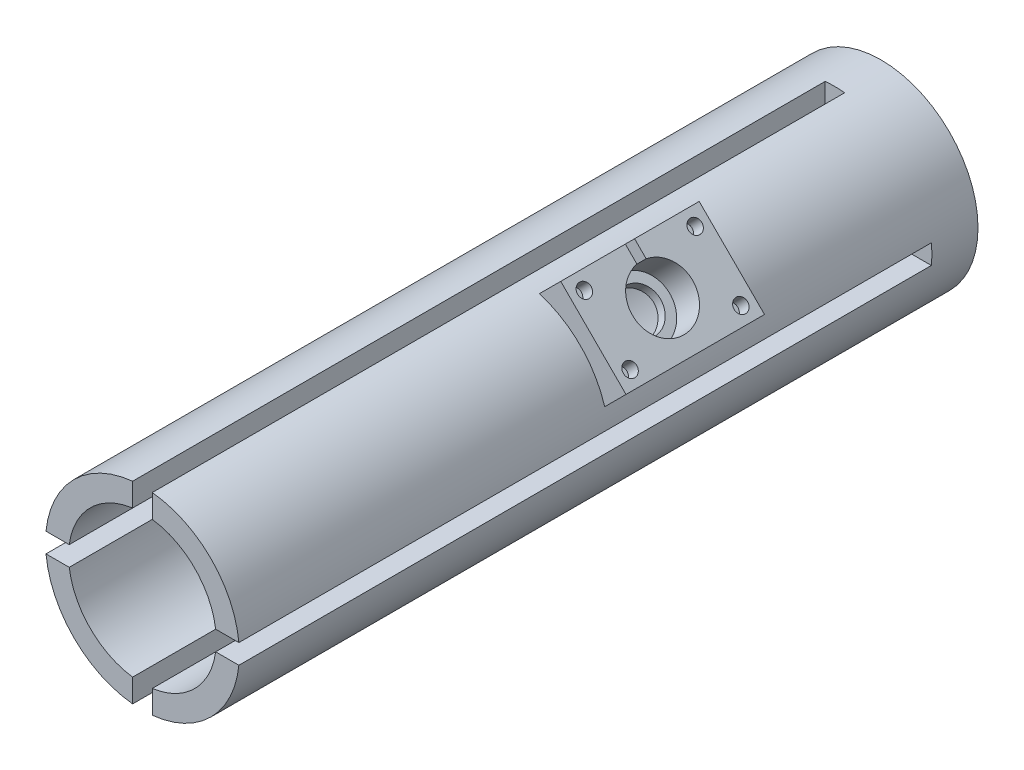
SolidWorks part; units mm, degrees
ref_plane "Front Plane" through (0, 0, 0) normal (0, 0, 1) x (1, 0, 0)
ref_plane "Top Plane" through (0, 0, 0) normal (0, 1, 0) x (1, 0, 0)
ref_plane "Right Plane" through (0, 0, 0) normal (1, 0, 0) x (0, 0, -1)
sketch "Sketch1" plane through (0, 0, 0) normal (0, 0, 1) x (1, 0, 0)
  line L0 (-26.67, 0) -> (26.67, 0) construction
  line L1 (0, 26.67) -> (0, -26.67) construction
  line L7 (-15.24, 2.6988) -> (-27.94, 2.6987)
  line L8 (-15.24, 2.6988) -> (-15.24, -2.6987)
  line L11 (-15.24, -2.6987) -> (-27.94, -2.6987)
  line L12 (-27.94, 2.6987) -> (-27.94, -2.6987)
  line L17 (-15.24, 2.6988) -> (-27.94, -2.6987) construction
  line L18 (-15.24, -2.6987) -> (-27.94, 2.6987) construction
  line L23 (2.6987, 15.24) -> (-2.6988, 15.24)
  line L24 (-2.6988, 15.24) -> (-2.6988, 27.94)
  line L26 (2.6987, 15.24) -> (2.6987, 27.94)
  line L27 (2.6987, 27.94) -> (-2.6988, 27.94)
  line L28 (2.6987, 15.24) -> (-2.6988, 27.94) construction
  line L29 (-2.6988, 15.24) -> (2.6987, 27.94) construction
  line L30 (26.67, 0) -> (-26.67, 0) construction
  line L31 (15.24, -2.6987) -> (15.24, 2.6988)
  line L32 (15.24, 2.6988) -> (27.94, 2.6988)
  line L33 (15.24, -2.6987) -> (27.94, -2.6987)
  line L34 (27.94, -2.6987) -> (27.94, 2.6988)
  line L35 (15.24, -2.6987) -> (27.94, 2.6988) construction
  line L36 (15.24, 2.6988) -> (27.94, -2.6987) construction
  line L37 (0, -26.67) -> (0, 26.67) construction
  line L38 (-2.6987, -15.24) -> (2.6988, -15.24)
  line L39 (2.6988, -15.24) -> (2.6988, -27.94)
  line L40 (-2.6987, -15.24) -> (-2.6987, -27.94)
  line L41 (-2.6987, -27.94) -> (2.6988, -27.94)
  line L42 (-2.6987, -15.24) -> (2.6988, -27.94) construction
  line L43 (2.6988, -15.24) -> (-2.6987, -27.94) construction
  line L44 (-18.8585, -18.8585) -> (18.5639, 18.5639) construction
  line L45 (7.1842, 25.1447) -> (25.1447, 7.1842)
  line L46 (7.1842, 25.1447) -> (13.4704, 31.4309)
  line L47 (25.1447, 7.1842) -> (31.4309, 13.4704)
  line L48 (13.4704, 31.4309) -> (31.4309, 13.4704)
  line L49 (22.4506, 22.4506) -> (16.1645, 16.1645) construction
  circle A10 centre (0, 0) radius 20.32
  circle A14 centre (0, 0) radius 26.67
  circle A15 centre (0, 0) radius 10.16
  point P7 (-21.59, 0)
  point P33 (0, 0)
  dimension "D1" = 40.64
  dimension "D4" = 12.7
  dimension "D5" = 4
  dimension "D7" = 45
  dimension "D8" = 25.4
  dimension "D9" = 8.89
  dimension "D6" = 20.32
  dimension "D10" = 22.86
  dimension "D11" = 15.24
  dimension "D3" = 5.3975
  dimension "D2" = 6.35
extrude "Boss-Extrude2" add sketch "Sketch1" along normal blind 203.2 contours L24 A14 L7 A10 | L47 A14 L46 L45 A10 | L32 A14 L47 L45 L46 L26 A10 | L39 A14 L33 A10 | L11 A14 L40 A10 region at (-15.5039, 15.5039, 0) region at (-15.5039, -15.5039, 0) region at (14.5551, 14.5551, 0) region at (15.5039, -15.5039, 0) region at (17.2574, 17.2574, 0)
extrude "Boss-Extrude3" add sketch "Sketch1<15>" along normal blind 12.7 contours L7 A10 L11 L8 | L26 A10 L24 L23 | L33 A10 L32 L31 | L40 A10 L39 L38 | L39 A14 L33 A10 | L11 A14 L40 A10 | L24 A14 L7 A10 | L32 A14 L47 L45 L46 L26 A10 | L47 A14 L46 L45 | L32 A10 L26 L23 L24 L7 L8 L11 L40 L38 L39 L33 L31 A15 | L26 A14 L24 A10 | L7 A14 L11 A10 | L40 A14 L39 A10 | L33 A14 L32 A10 region at (-17.7503, 0, 0) region at (-17.69, 3.2684, 0) region at (-23.4422, 0, 0) region at (-15.5039, 15.5039, 0) region at (0, 17.7503, 0) region at (0, 23.4422, 0) region at (-15.5039, -15.5039, 0) region at (14.5551, 14.5551, 0) region at (0, -23.4422, 0) region at (0, -17.7503, 0) region at (17.7503, 0, 0) region at (23.4422, 0, 0) region at (15.5039, -15.5039, 0) region at (17.2574, 17.2574, 0)
sketch "Sketch1<15>" plane through (0, 0, 0) normal (0, 0, 1) x (1, 0, 0) same geometry as "Sketch1"
extrude "Boss-Extrude4" add sketch "Sketch1<18>" along normal blind 101.6 contours A14 L47 L48 L46 region at (20.2329, 20.2329, 0)
sketch "Sketch1<18>" plane through (0, 0, 0) normal (0, 0, 1) x (1, 0, 0) same geometry as "Sketch1"
extrude "Cut-Extrude2" cut sketch "Sketch1<19>" along normal blind 63.5 contours A14 L47 L48 L46 region at (20.2329, 20.2329, 0)
sketch "Sketch1<19>" plane through (0, 0, 0) normal (0, 0, 1) x (1, 0, 0) same geometry as "Sketch1"
sketch "Sketch4" plane through (22.4506, 22.4506, 0) normal (0.7071, 0.7071, 0) x (0, 0, -1)
  line L0 (-82.55, -12.7) -> (-82.55, 12.7) construction
  line L1 (-101.6, -12.7) -> (-63.5, -12.7) construction
  line L2 (-101.6, 12.7) -> (-63.5, 12.7) construction
  circle A0 centre (-82.55, 0) radius 8.3
  dimension "D1" = 16.6
extrude "Cut-Extrude3" cut sketch "Sketch4" against normal blind 8.89
sketch "Sketch5" plane through (22.4506, 22.4506, 0) normal (0.7071, 0.7071, 0) x (0, 0, -1)
  line L0 (-82.55, -12.7) -> (-82.55, 12.7) construction
  line L4 (-63.5, -12.7) -> (-63.5, 12.7)
  line L5 (-63.5, 12.7) -> (-101.6, 12.7)
  line L6 (-101.6, 12.7) -> (-101.6, -12.7)
  line L7 (-101.6, -12.7) -> (-63.5, -12.7)
  line L9 (-63.5, 12.7) -> (-101.6, 12.7)
  line L10 (-101.6, 12.7) -> (-101.6, -12.7)
  line L11 (-101.6, -12.7) -> (-63.5, -12.7)
  line L14 (-63.5, -12.7) -> (-63.5, 12.7)
  circle A1 centre (-95.25, -5.715) radius 1.5875 construction
  circle A2 centre (-95.25, 5.715) radius 1.5875 construction
  circle A4 centre (-95.25, -5.715) radius 1.5875 construction
  circle A5 centre (-95.25, 5.715) radius 1.5875 construction
  circle A6 centre (-69.85, 5.715) radius 1.5875 construction
  circle A7 centre (-69.85, -5.715) radius 1.5875 construction
  circle A8 centre (-95.25, -5.715) radius 2.5781
  circle A9 centre (-95.25, 5.715) radius 2.5781
  circle A10 centre (-69.85, 5.715) radius 2.5781
  circle A11 centre (-69.85, -5.715) radius 2.5781
  circle A12 centre (-82.55, 0) radius 5.715
  dimension "D2" = 5.1562
  dimension "D3" = 11.43
  dimension "D1" = 0
extrude "Cut-Extrude5" cut sketch "Sketch5" against normal blind 25.4 contours A12 region at (22.4506, 22.4506, 82.55)
sketch "Sketch7" plane through (-8.9803, 8.9803, 0) normal (-0.7071, 0.7071, 0) x (0, 0, 1)
  line L0 (82.55, 33.02) -> (82.55, 23.723) construction
  line L1 (63.5, 33.02) -> (101.6, 33.02) construction
  line L2 (101.6, 31.75) -> (63.5, 31.75) construction
  line L3 (81.28, 25.75) -> (83.82, 25.75)
  line L4 (81.28, 25.75) -> (81.28, 31.75)
  line L5 (81.28, 31.75) -> (83.82, 31.75)
  line L6 (83.82, 25.75) -> (83.82, 31.75)
  line L7 (81.28, 25.75) -> (83.82, 31.75) construction
  line L8 (81.28, 31.75) -> (83.82, 25.75) construction
  point P4 (82.55, 28.75)
  dimension "D1" = 2.54
  dimension "D2" = 6
extrude "Cut-Extrude6" cut sketch "Sketch7" against normal blind 8.89
sketch "Sketch8" plane through (22.4506, 22.4506, 0) normal (0.7071, 0.7071, 0) x (0, 0, -1)
  line L0 (-82.55, -12.7) -> (-82.55, 12.7) construction
  line L1 (-97.79, 12.7) -> (-97.79, -12.7) construction
  line L2 (-101.6, -12.7) -> (-63.5, -12.7) construction
  line L4 (-63.5, -12.7) -> (-63.5, 12.7)
  line L5 (-63.5, 12.7) -> (-81.28, 12.7)
  line L6 (-101.6, 12.7) -> (-101.6, -12.7)
  line L7 (-101.6, -12.7) -> (-63.5, -12.7)
  line L8 (-63.5, -12.7) -> (-63.5, 12.7)
  line L9 (-63.5, 12.7) -> (-82.55, 12.7)
  line L10 (-101.6, 12.7) -> (-101.6, -12.7)
  line L11 (-101.6, -12.7) -> (-63.5, -12.7)
  line L16 (-83.82, 8.2023) -> (-83.82, 12.7)
  line L17 (-83.82, 8.2023) -> (-83.82, 12.7)
  line L18 (-83.82, 12.7) -> (-101.6, 12.7)
  line L19 (-82.55, 12.7) -> (-101.6, 12.7)
  line L20 (-81.28, 12.7) -> (-81.28, 8.2023)
  line L21 (-81.28, 12.7) -> (-81.28, 8.2023)
  circle A6 centre (-97.79, 8.89) radius 1.8542
  circle A7 centre (-97.79, -8.89) radius 1.8542
  circle A8 centre (-67.31, -8.89) radius 1.8542
  circle A9 centre (-67.31, 8.89) radius 1.8542
  arc A10 (-83.82, 8.2023) -> (-81.28, 8.2023) centre (-82.55, 0) ccw
  arc A11 (-83.82, 8.2023) -> (-81.28, 8.2023) centre (-82.55, 0) ccw
  dimension "D2" = 3.7084
  dimension "D4" = 3.81
  dimension "D5" = 5.6642
  dimension "D3" = 3.81
  dimension "D1" = 0
extrude "Cut-Extrude7" cut sketch "Sketch8" against normal blind 3.81 contours A7 | A6 | A9 | A8 region at (16.1645, 28.7368, 97.79) region at (28.7368, 16.1645, 97.79) region at (28.7368, 16.1645, 67.31) region at (16.1645, 28.7368, 67.31)
